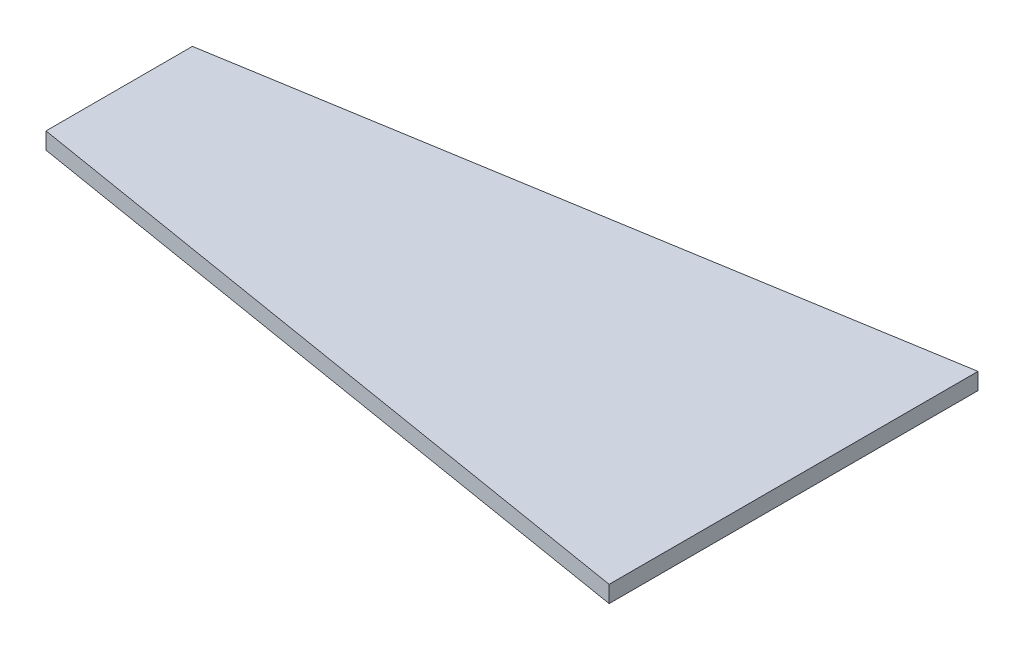
SolidWorks part; units mm, degrees
ref_plane "Front Plane" through (0, 0, 0) normal (0, 0, 1) x (1, 0, 0)
ref_plane "Top Plane" through (0, 0, 0) normal (0, 1, 0) x (1, 0, 0)
ref_plane "Right Plane" through (0, 0, 0) normal (1, 0, 0) x (0, 0, -1)
sketch "Sketch1" plane through (0, 0, 0) normal (0, 1, 0) x (1, 0, 0)
  line L1 (0, 0) -> (263.3435, 0)
  line L2 (0, 0) -> (0, 204.1914)
  line L3 (0, 204.1914) -> (263.3435, 204.1914)
  line L4 (263.3435, 0) -> (263.3435, 204.1914)
  line L5 (0, 0) -> (263.3435, 204.1914) construction
  line L6 (0, 204.1914) -> (263.3435, 0) construction
  point P4 (131.6717, 102.0957)
  dimension "D1" = 263.3435
  dimension "D2" = 204.1914
extrude "Boss-Extrude1" add sketch "Sketch1" along normal blind 4.6
sketch "Sketch2" plane through (0, 0, 0) normal (0, -1, 0) x (1, 0, 0)
  line L8 (273.0046, -21.7914) -> (263.3435, -21.7914)
  line L9 (273.0046, -123.3914) -> (273.0046, -21.7914)
  line L10 (263.3435, -123.3914) -> (273.0046, -123.3914)
  line L11 (263.3435, -21.7914) -> (263.3435, -123.3914)
  line L14 (263.3435, -123.3914) -> (187.6419, -199.544)
  line L15 (263.3939, -21.8421) -> (246.2539, -4.6)
  line L16 (37.9813, -92.7414) -> (77.7444, -92.7414)
  line L17 (37.9813, -52.4414) -> (37.9813, -92.7414)
  line L18 (37.9813, -52.4414) -> (77.7444, -52.4414)
  line L19 (77.7444, -52.4414) -> (77.7444, -92.7414)
  line L20 (263.3939, -21.8421) -> (77.7444, -52.4414)
  line L21 (77.7444, -92.7414) -> (263.3435, -123.3914)
  line M7 (263.3435, -204.1914) -> (263.3435, 0)
extrude "Cut-Extrude1" cut sketch "Sketch2" against normal through all flip side to cut contours L19 L21 L20 M7 region at (183.8996, 0, -72.6083)
equation "\"MDF\"= 4.8mm"
equation "\"Foamcore\"= 4.6mm"
equation "\"GMaterial\"= \"MDF\""
equation "\"PCB\" = 1.6mm"
equation "\"BaseWidth\" = 10in"
equation "\"SkidLength\" = 1in"
equation "\"SkidClearance\" = 0.4in"
equation "\"MotorMountLength\" = 2in"
equation "\"MotorMountWidth\" = \"GMaterial\""
equation "\"MotorMountHeight\" = 2.25in"
equation "\"UnoStackWidth\" = 77.4mm"
equation "\"UnoStackLength\" = 79.8mm"
equation "\"UnoStackHeight\" = 34.2mm"
equation "\"TallHexRiserHeight\" = 22.2mm"
equation "\"PingPongBallSize\" = 40mm"
equation "\"BarrelLength\" = 9in"
equation "\"BarrelSize\" = \"PingPongBallSize\""
equation "\"PlatformLength\" = 4in"
equation "\"PlatformWidth\" = 6in"
equation "\"WheelDiameter\"=2.99213"
equation "\"ServoMountHeight\"=2.49223"
equation "\"ServoGearHeight\" = 0.95330261in"
equation "\"ServoMountLength\"= 1.53774"
equation "\"PivotHoleRadius\"= 0.616358"
equation "\"PlatformMountHeight\" = 3.19"
equation "\"TensionOffSet\"= .3mm"
equation "\"MotorMountWedge\"=0.333333"
equation "\"LaserCutterOffset\"= .3mm"
equation "\"BumperWidth\"=11"
equation "\"PitcherWheelCompression\" = 2.5mm"
equation "\"BarrelToHopperDistance\" = 0.5405in"
equation "\"PitchingWheelWidth\" = 26.2mm"
equation "\"PitchingWheelDiameter\" = 65.5mm"
equation "\"PitchingWheelMountOffset\" = 8.4mm"
equation "\"PitchingWheelInnerDiameter\" = 45.5mm"
equation "\"PitchingWheelBoltShoulder\" = 4.5mm"
equation "\"BrassCouplingLength\" = 18mm"
equation "\"PitchingMotorHeight\" = 57.0mm"
equation "\"PitchingMotorShaftTopHeight\" = \"PitchingMotorHeight\" - 44.1mm"
equation "\"PitchingMotorBodyHeight\" = 38mm"
equation "\"PitchingMotorTopShoulderHeight\" = 40.6mm - \"PitchingMotorBodyHeight\" "
equation "\"PitchingMotorBottomShoulderHeight\" = 40.2mm - \"PitchingMotorBodyHeight\""
equation "\"PitchingMotorBottomShaftHeight\" = \"PitchingMotorHeight\" - \"PitchingMotorShaftTopHeight\" - \"PitchingMotorTopShoulderHeight\" - \"PitchingMotorBodyHeight\" - \"PitchingMotorBottomShoulderHeight\""
equation "\"PitchingMotorShaftDiameter\" = 2.2mm"
equation "\"PitchingMotorBodyDiameter\" = 27.4mm"
equation "\"PitchingMotorTopShoulderDiameter\" = 9.8mm"
equation "\"PitchingMotorBottomShoulderDiameter\" = 9.8mm"
equation "\"BrassCouplingHexSize\" = 12mm"
equation "\"BrassCouplingBoreSize\" = 3.17mm"
equation "\"PitchingMotorMountingHoleDistance\" = 16mm"
equation "\"Acrylic\" = 4.4mm"
equation "\"PitchingMotorDistance\" = \"PitchingWheelDiameter\" + \"PingPongBallSize\" - \"PitcherWheelCompression\"*2"
equation "\"PitchingMotorPlatformOffset\"=1"
equation "\"ServoPlatformOffset\"=1.64173"
equation "\"BallBearingDiameter\" = 22mm"
equation "\"BallBearingWidth\" = 9mm"
equation "\"BallBearingHexShoulder\" = 9mm - 5.9mm"
equation "\"BallBearingHexSize\" = .36in"
equation "\"PlatformMountFootLength\"=0.857143"
equation "\"WheelWidth\"= 26mm"
equation "\"ServoMountReductionBackHeight\"=2.25"
equation "\"PlatformBottomWidthThird\" =  0.857143in"
equation "\"PlatformMountBackReductionHeight\"= 2.5in"
equation "\"PlatformMountBackReductionWidth\"= 3/7in"
equation "\"PlatformMountFrontReductionWidth\" =  1.46226in"
equation "\"PlatformMountFrontReductionHeight\" = 2.5in"
equation "\"HopperLongWallLength\" = 8.646in"
equation "\"HopperShortWallLength\" = 0.9571in"
equation "\"HopperHeight\" = 3.50in - \"Foamcore\""
equation "\"HoperLongSlantLength\" = 7.064in"
equation "\"HopperBottomTemplateWidth\" = 8.03903165in"
equation "\"HopperBottomTemplateLength\" = 10.367854in"
equation "\"D1@Sketch1\"=\"HopperBottomTemplateLength\""
equation "\"D2@Sketch1\"=\"HopperBottomTemplateWidth\""
equation "\"D1@Boss-Extrude1\"=\"Foamcore\""
